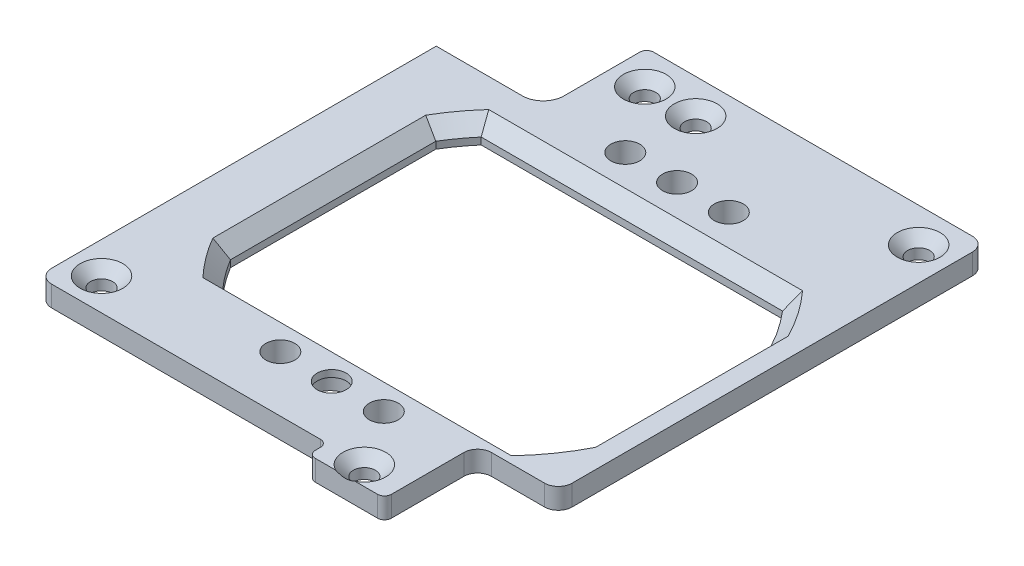
SolidWorks part; units mm, degrees
ref_plane "Спереди" through (0, 0, 0) normal (0, 0, 1) x (1, 0, 0)
ref_plane "Сверху" through (0, 0, 0) normal (0, 1, 0) x (1, 0, 0)
ref_plane "Справа" through (0, 0, 0) normal (1, 0, 0) x (0, 0, -1)
sketch "Sketch1" plane through (0, 6.6, 0) normal (0, 1, 0) x (1, 0, 0)
  line L0 (21.8386, 16.5986) -> (-21.8386, 16.5986)
  line L1 (-24.6, 12.7796) -> (-24.6, -16.9796)
  line L2 (-21.4766, -21.2133) -> (21.4766, -21.2133)
  line L3 (25.4, -15.5686) -> (25.4, 11.3686)
  line L4 (7.5516, -26.9) -> (7.5516, 23.1) construction
  line L5 (7.5516, 23.1) -> (-7.4484, 23.1) construction
  line L6 (-7.4484, 23.1) -> (-7.4484, -26.9) construction
  line L7 (-7.4484, -26.9) -> (7.5516, -26.9) construction
  line L8 (7.5516, -26.9) -> (-7.4484, 23.1) construction
  line L9 (7.5516, 23.1) -> (-7.4484, -26.9) construction
  line L10 (-32.5, 22.75) -> (-34.5, 22.75)
  line L45 (-34.5, 22.75) -> (-34.5, -32.9854)
  line L46 (-32.5, -34.9854) -> (6.4639, -34.9854)
  line L47 (7.4639, -35.9854) -> (7.4639, -36.75)
  line L48 (8.4639, -37.75) -> (17.5, -37.75)
  line L49 (18.5, -36.75) -> (18.5, -26.25)
  line L50 (20.5, -24.25) -> (28.1923, -24.25)
  line L51 (30.1923, -22.25) -> (30.1923, 35.75)
  line L52 (28.1923, 37.75) -> (-11.2951, 37.75)
  line L56 (-11.2951, 37.75) -> (-18, 37.75)
  line L57 (-19, 36.75) -> (-19, 25.75)
  line L58 (-22, 22.75) -> (-32.5, 22.75)
  circle A0 centre (7.5516, 23.1) radius 2.1
  circle A1 centre (0.0516, 23.1) radius 2.1
  circle A2 centre (-7.4484, 23.1) radius 2.1
  circle A3 centre (7.5516, -26.9) radius 2.1
  circle A4 centre (0, -26.9) radius 2.1
  circle A5 centre (-7.4484, -26.9) radius 2.1
  arc A6 (21.8386, 16.5986) -> (25.4, 11.3686) centre (0, -2.1) cw
  arc A7 (25.4, -15.5686) -> (21.4766, -21.2133) centre (0, -2.1) cw
  arc A8 (-21.4766, -21.2133) -> (-24.6, -16.9796) centre (0, -2.1) cw
  arc A9 (-21.8386, 16.5986) -> (-24.6, 12.7796) centre (0, -2.1) ccw
  circle A10 centre (25.4, 32.7663) radius 1.6
  circle A11 centre (-29.9119, -30.3479) radius 1.6
  circle A12 centre (-14.2971, 32.7663) radius 1.6
  circle A13 centre (12.8146, -34.9854) radius 1.6
  circle A14 centre (-6.9188, 32.7663) radius 1.6
  arc A45 (-34.5, -32.9854) -> (-32.5, -34.9854) centre (-32.5, -32.9854) ccw
  arc A46 (7.4639, -35.9854) -> (6.4639, -34.9854) centre (6.4639, -35.9854) ccw
  arc A47 (7.4639, -36.75) -> (8.4639, -37.75) centre (8.4639, -36.75) ccw
  arc A48 (17.5, -37.75) -> (18.5, -36.75) centre (17.5, -36.75) ccw
  arc A49 (20.5, -24.25) -> (18.5, -26.25) centre (20.5, -26.25) ccw
  arc A50 (28.1923, -24.25) -> (30.1923, -22.25) centre (28.1923, -22.25) ccw
  arc A51 (30.1923, 35.75) -> (28.1923, 37.75) centre (28.1923, 35.75) ccw
  arc A56 (-18, 37.75) -> (-19, 36.75) centre (-18, 36.75) ccw
  arc A57 (-22, 22.75) -> (-19, 25.75) centre (-22, 25.75) ccw
  dimension "D1" = 27.0516
  dimension "D2" = 27.0516
  dimension "D3" = 22.6407
  dimension "D4" = 22.6407
extrude "Boss-Extrude1" add sketch "Sketch1" against normal blind 3
chamfer "Chamfer1" distance 2 angle 45 8 edges at (23.7636, 6.6, -14.0819) (25.4, 6.6, 2.1) (23.6076, 6.6, 18.5086) (0, 6.6, 21.2133) (-23.1353, 6.6, 19.1681) (-24.6, 6.6, 2.1) (0, 6.6, -16.5986) (-23.2977, 6.6, -14.7458)
sketch "Sketch2" plane through (0, 3.6, 0) normal (0, -1, 0) x (1, 0, 0)
  circle A0 centre (0, 27.1) radius 2.7345
extrude "Cut-Extrude1" cut sketch "Sketch2" against normal blind 2
chamfer "Chamfer2" distance 1.5 angle 45 5 edges at (-14.2971, 6.6, -31.1663) (25.4, 6.6, -31.1663) (12.8146, 6.6, 36.5854) (-29.9119, 6.6, 31.9479) (-6.9188, 6.6, -31.1663)
